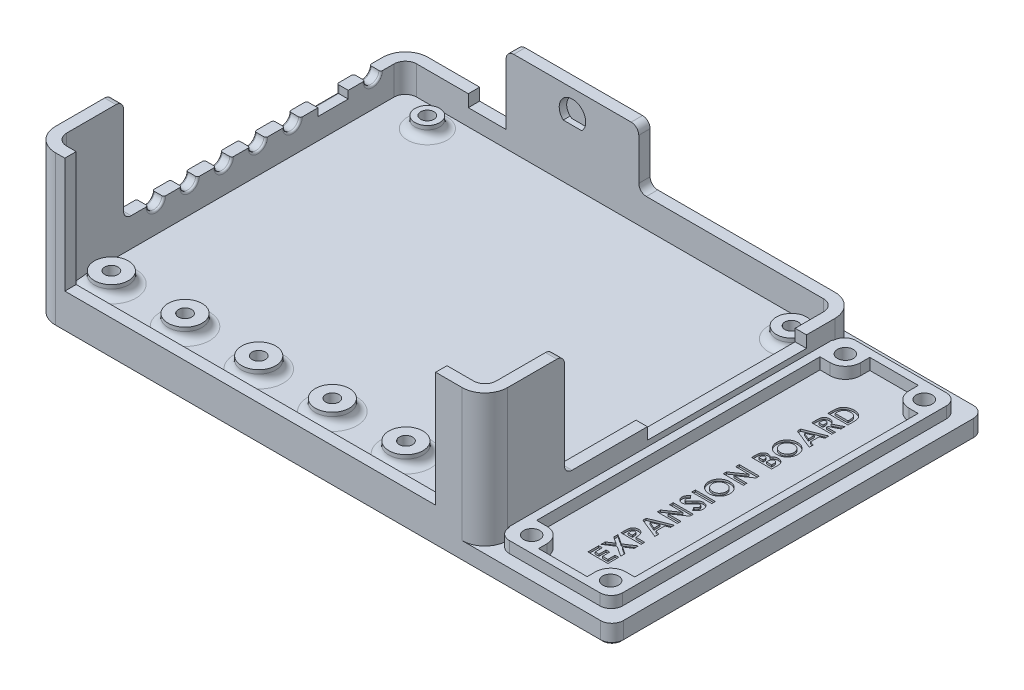
SolidWorks part; units mm, degrees
ref_plane "Front Plane" through (0, 0, 0) normal (0, 0, 1) x (1, 0, 0)
ref_plane "Top Plane" through (0, 0, 0) normal (0, 1, 0) x (1, 0, 0)
ref_plane "Right Plane" through (0, 0, 0) normal (1, 0, 0) x (0, 0, -1)
sketch "Sketch1" plane through (0, 0, 0) normal (0, 1, 0) x (1, 0, 0)
  line L1 (-53.7, 46.2) -> (53.7, 46.2)
  line L2 (-56.7, 43.2) -> (-56.7, -43.2)
  line L3 (-53.7, -46.2) -> (53.7, -46.2)
  line L4 (56.7, 43.2) -> (56.7, -43.2)
  line L5 (-56.7, 46.2) -> (56.7, -46.2) construction
  line L6 (-56.7, -46.2) -> (56.7, 46.2) construction
  arc A0 (-56.7, -43.2) -> (-53.7, -46.2) centre (-53.7, -43.2) ccw
  arc A1 (53.7, -46.2) -> (56.7, -43.2) centre (53.7, -43.2) ccw
  arc A2 (53.7, 46.2) -> (56.7, 43.2) centre (53.7, 43.2) cw
  arc A3 (-53.7, 46.2) -> (-56.7, 43.2) centre (-53.7, 43.2) ccw
  point P0 (0, 0)
  dimension "D3" = 3
  dimension "D1" = 113.4
  dimension "D2" = 92.4
extrude "Boss-Extrude1" add sketch "Sketch1" along normal blind 5
sketch "Sketch2" plane through (0, 0, 0) normal (0, -1, 0) x (1, 0, 0)
  line L12 (-56.7, 43.2) -> (-56.7, -43.2)
  line L13 (-53.7, -46.2) -> (53.7, -46.2)
  line L14 (56.7, -43.2) -> (56.7, 43.2)
  line L15 (53.7, 46.2) -> (-53.7, 46.2)
  line L16 (-56.7, 43.2) -> (-56.7, -43.2)
  line L17 (-53.7, -46.2) -> (53.7, -46.2)
  line L18 (56.7, -43.2) -> (56.7, 43.2)
  line L19 (53.7, 46.2) -> (-53.7, 46.2)
  line L24 (-59.7, 43.2) -> (-59.7, -43.2)
  line L25 (-53.7, -49.2) -> (53.7, -49.2)
  line L26 (59.7, -43.2) -> (59.7, 43.2)
  line L27 (53.7, 49.2) -> (-53.7, 49.2)
  line L28 (-59.7, 43.2) -> (-59.7, -43.2)
  line L29 (-53.7, -49.2) -> (53.7, -49.2)
  line L30 (59.7, -43.2) -> (59.7, 43.2)
  line L31 (53.7, 49.2) -> (-53.7, 49.2)
  arc A12 (-53.7, 46.2) -> (-56.7, 43.2) centre (-53.7, 43.2) ccw
  arc A13 (-56.7, -43.2) -> (-53.7, -46.2) centre (-53.7, -43.2) ccw
  arc A14 (53.7, -46.2) -> (56.7, -43.2) centre (53.7, -43.2) ccw
  arc A15 (56.7, 43.2) -> (53.7, 46.2) centre (53.7, 43.2) ccw
  arc A16 (-53.7, 46.2) -> (-56.7, 43.2) centre (-53.7, 43.2) ccw
  arc A17 (-56.7, -43.2) -> (-53.7, -46.2) centre (-53.7, -43.2) ccw
  arc A18 (53.7, -46.2) -> (56.7, -43.2) centre (53.7, -43.2) ccw
  arc A19 (56.7, 43.2) -> (53.7, 46.2) centre (53.7, 43.2) ccw
  arc A24 (-53.7, 49.2) -> (-59.7, 43.2) centre (-53.7, 43.2) ccw
  arc A25 (-59.7, -43.2) -> (-53.7, -49.2) centre (-53.7, -43.2) ccw
  arc A26 (53.7, -49.2) -> (59.7, -43.2) centre (53.7, -43.2) ccw
  arc A27 (59.7, 43.2) -> (53.7, 49.2) centre (53.7, 43.2) ccw
  arc A28 (-53.7, 49.2) -> (-59.7, 43.2) centre (-53.7, 43.2) ccw
  arc A29 (-59.7, -43.2) -> (-53.7, -49.2) centre (-53.7, -43.2) ccw
  arc A30 (53.7, -49.2) -> (59.7, -43.2) centre (53.7, -43.2) ccw
  arc A31 (59.7, 43.2) -> (53.7, 49.2) centre (53.7, 43.2) ccw
  dimension "D1" = 0
  dimension "D2" = 3
extrude "Boss-Extrude2" add sketch "Sketch2" against normal blind 40
sketch "Sketch3" plane through (0, 0, 0) normal (0, -1, 0) x (1, 0, 0)
  line L0 (53.7, 49.2) -> (-53.7, 49.2) construction
  line L1 (39.3485, 49.2) -> (94.7, 49.2)
  line L2 (39.3485, 49.2) -> (39.3485, -49.2)
  line L3 (39.3485, -49.2) -> (94.7, -49.2)
  line L4 (94.7, 49.2) -> (94.7, -49.2)
  line L5 (59.7, -43.2) -> (59.7, 43.2) construction
  line L6 (-53.7, -49.2) -> (53.7, -49.2) construction
  dimension "D1" = 35
extrude "Boss-Extrude3" add sketch "Sketch3" against normal blind 5
sketch "Sketch4" plane through (0, 40, 0) normal (0, 1, 0) x (1, 0, 0)
  line L0 (-56.7, 43.2) -> (-56.7, -43.2) construction
  line L1 (-51.2, -37.1427) -> (46.7, -37.1427)
  line L2 (-51.2, -37.1427) -> (-51.2, -59.8991)
  line L3 (-51.2, -59.8991) -> (46.7, -59.8991)
  line L4 (46.7, -37.1427) -> (46.7, -59.8991)
  line L5 (56.7, 43.2) -> (56.7, -43.2) construction
  dimension "D1" = 5.5
  dimension "D2" = 10
extrude "Cut-Extrude1" cut sketch "Sketch4" against normal offset from surface (30.4 mm away) 4.6 up to face at (0, 5, 0)
sketch "Sketch7" plane through (0, 5, 0) normal (0, 1, 0) x (1, 0, 0)
  line L0 (-51.3, -36.8) -> (45.92, -36.8) construction
  line L1 (51.042, 40.404) -> (-45.097, 40.404) construction
  line L3 (-56.7, 0) -> (56.7, 0) construction
  line L4 (-56.7, -43.2) -> (-56.7, 43.2) construction
  line L5 (56.7, -43.2) -> (56.7, 43.2) construction
  line L6 (-56.7, 43.2) -> (-56.7, -43.2) construction
  line L7 (0, 46.2) -> (0, -46.2) construction
  line L8 (-53.7, 46.2) -> (53.7, 46.2) construction
  line L9 (-53.7, -46.2) -> (53.7, -46.2) construction
  line L10 (46.7, -46.2) -> (-51.2, -46.2) construction
  circle A0 centre (-51.3, -36.8) radius 1.75
  circle A1 centre (-31.86, -36.8) radius 1.75
  circle A2 centre (-12.41, -36.8) radius 1.75
  circle A3 centre (7.03, -36.8) radius 1.75
  circle A4 centre (26.46, -36.8) radius 1.75
  circle A5 centre (45.92, -36.8) radius 1.75
  circle A6 centre (-45.097, 40.404) radius 1.75
  circle A7 centre (51.042, 40.404) radius 1.75
  circle A8 centre (-45.097, 40.404) radius 3.25
  circle A9 centre (51.042, 40.404) radius 4
  circle A10 centre (45.92, -36.8) radius 4.5
  circle A11 centre (26.46, -36.8) radius 4.5
  circle A12 centre (7.03, -36.8) radius 4.5
  circle A13 centre (-12.41, -36.8) radius 4.5
  circle A14 centre (-31.86, -36.8) radius 4.5
  circle A15 centre (-51.3, -36.8) radius 4.5
  dimension "D1" = 3.5
  dimension "D2" = 3.5
  dimension "D3" = 3.5
  dimension "D4" = 3.5
  dimension "D5" = 3.5
  dimension "D6" = 3.5
  dimension "D7" = 3.5
  dimension "D8" = 3.5
  dimension "D19" = 9
  dimension "D20" = 9
  dimension "D21" = 9
  dimension "D22" = 9
  dimension "D23" = 9
  dimension "D24" = 9
  dimension "D25" = 8
  dimension "D26" = 6.5
  dimension "D9" = 77.204
  dimension "D10" = 6.203
  dimension "D11" = 5.122
  dimension "D12" = 19.44
  dimension "D13" = 19.45
  dimension "D14" = 19.44
  dimension "D15" = 19.43
  dimension "D16" = 19.46
  dimension "D17" = 5.4
  dimension "D18" = 9.4
extrude "Boss-Extrude5" add sketch "Sketch7" along normal offset from surface (3 mm away) 1.6 up to face at (-2.25, 9.6, 47.7)
fillet "Fillet2" radius 2 8 edges at (45.92, 5, 41.3) (26.46, 5, 41.3) (7.03, 5, 41.3) (-12.41, 5, 41.3) (-31.86, 5, 41.3) (-51.3, 5, 41.3) (51.042, 5, -36.404) (-45.097, 5, -37.154)
sketch "Sketch11" plane through (-59.7, 0, 0) normal (-1, 0, 0) x (0, 0, 1)
  line L0 (-37.613, 12.6) -> (19.667, 12.6) construction
  line L1 (43.2, 0) -> (-43.2, 0) construction
  line L3 (-37.613, 12.6) -> (-43.2, 12.6) construction
  line L4 (-43.2, 40) -> (-43.2, 0) construction
  circle A0 centre (19.667, 12.6) radius 2.1
  circle A1 centre (10.777, 12.6) radius 2.1
  circle A2 centre (1.757, 12.6) radius 2.1
  circle A3 centre (-7.26, 12.6) radius 2.1
  circle A4 centre (-16.404, 12.6) radius 2.1
  circle A5 centre (-37.613, 12.6) radius 2.1
  dimension "D7" = 4.2
  dimension "D8" = 4.2
  dimension "D9" = 4.2
  dimension "D10" = 4.2
  dimension "D11" = 4.2
  dimension "D12" = 4.2
  dimension "D1" = 12.6
  dimension "D2" = 21.209
  dimension "D3" = 9.144
  dimension "D4" = 9.017
  dimension "D5" = 9.02
  dimension "D6" = 8.89
  dimension "D13" = 5.587
extrude "Cut-Extrude4" cut sketch "Sketch11" against normal blind 9.6
sketch "Sketch12" plane through (-59.7, 0, 0) normal (-1, 0, 0) x (0, 0, 1)
  line L0 (43.2, 40) -> (-43.2, 40) construction
  line L1 (28.2, 40) -> (-56.9577, 40)
  line L2 (28.2, 40) -> (28.2, 12.6)
  line L3 (28.2, 12.6) -> (-56.9577, 12.6)
  line L4 (-56.9577, 40) -> (-56.9577, 12.6)
  line L5 (43.2, 0) -> (-43.2, 0) construction
  dimension "D1" = 21
  dimension "D2" = 12.6
extrude "Cut-Extrude5" cut sketch "Sketch12" against normal through all
sketch "Sketch13" plane through (0, 12.6, 0) normal (0, 1, 0) x (1, 0, 0)
  line L0 (-45.097, 40.404) -> (-35.077, 40.404) construction
  line L2 (-40.077, 53.0138) -> (-30.077, 53.0138)
  line L3 (-40.077, 53.0138) -> (-40.077, 27.7942)
  line L4 (-40.077, 27.7942) -> (-30.077, 27.7942)
  line L5 (-30.077, 53.0138) -> (-30.077, 27.7942)
  line L6 (-40.077, 53.0138) -> (-30.077, 27.7942) construction
  line L7 (-40.077, 27.7942) -> (-30.077, 53.0138) construction
  dimension "D1" = 10.02
  dimension "D2" = 10
extrude "Cut-Extrude6" cut sketch "Sketch13" against normal offset from surface (3.2 mm away) 1.4 up to face at (-45.097, 8, -38.654)
sketch "Sketch14" plane through (0, 12.6, 0) normal (0, 1, 0) x (1, 0, 0)
  line L0 (51.042, 40.404) -> (51.042, 35.704) construction
  line L1 (45.5852, 35.704) -> (71.3808, 35.704)
  line L2 (45.5852, 35.704) -> (45.5852, -6.296)
  line L3 (45.5852, -6.296) -> (71.3808, -6.296)
  line L4 (71.3808, 35.704) -> (71.3808, -6.296)
  dimension "D1" = 42
  dimension "D2" = 4.7
extrude "Cut-Extrude7" cut sketch "Sketch14" against normal offset from surface (3.1 mm away) 1.5 up to face at (51.042, 8, -38.654)
sketch "Sketch15" plane through (0, 12.6, 0) normal (0, 1, 0) x (1, 0, 0)
  line L0 (53.7, 46.2) -> (-30.077, 46.2) construction
  line L1 (-30.077, 49.2) -> (4.923, 49.2)
  line L2 (-30.077, 49.2) -> (-30.077, 46.2)
  line L3 (-30.077, 46.2) -> (4.923, 46.2)
  line L4 (4.923, 49.2) -> (4.923, 46.2)
  dimension "D1" = 35
extrude "Boss-Extrude6" add sketch "Sketch15" along normal blind 15
fillet "Fillet3" radius 2 7 edges at (-58.2, 40, 28.2) (58.2, 40, 28.2) (58.2, 12.6, 28.2) (4.923, 12.6, -47.7) (4.923, 27.6, -47.7) (-30.077, 27.6, -47.7) (-58.2, 12.6, 28.2)
sketch "Sketch16" plane through (0, 0, -49.2) normal (0, 0, -1) x (-1, 0, 0)
  line L0 (10.1275, 19.1) -> (15.0265, 19.1)
  line L2 (-46.7, 9.6) -> (51.2, 9.6) construction
  line L3 (30.077, 25.6) -> (30.077, 9.4) construction
  arc A0 (15.0265, 19.1) -> (10.1275, 19.1) centre (12.577, 21.6) ccw
  dimension "D1" = 7
  dimension "D2" = 2.5
  dimension "D3" = 12
  dimension "D4" = 17.5
extrude "Cut-Extrude8" cut sketch "Sketch16" against normal up to surface (3 mm away) up to face at (-3.1349, 14.0416, -46.2)
sketch "Sketch17" plane through (0, 0, -49.2) normal (0, 0, -1) x (-1, 0, 0)
  circle A0 centre (12.577, 21.6) radius 3.0287
extrude "Boss-Extrude7" add sketch "Sketch17" against normal blind 1.5
sketch "Sketch18" plane through (0, 8, 0) normal (0, 1, 0) x (1, 0, 0)
  circle A0 centre (-51.3, -36.8) radius 1.75
  circle A1 centre (-31.86, -36.8) radius 1.75
  circle A2 centre (-12.41, -36.8) radius 1.75
  circle A3 centre (7.03, -36.8) radius 1.75
  circle A4 centre (26.46, -36.8) radius 1.75
  circle A5 centre (45.92, -36.8) radius 1.75
  circle A6 centre (51.042, 40.404) radius 1.75
  circle A7 centre (-45.097, 40.404) radius 1.75
extrude "Cut-Extrude9" cut sketch "Sketch18" against normal through all
sketch "Sketch19" plane through (0, 0, 0) normal (0, -1, 0) x (1, 0, 0)
  circle A0 centre (-51.3, 36.8) radius 2.9
  circle A1 centre (-31.86, 36.8) radius 2.9
  circle A2 centre (-12.41, 36.8) radius 2.9
  circle A3 centre (7.03, 36.8) radius 2.9
  circle A4 centre (26.46, 36.8) radius 2.9
  circle A5 centre (45.92, 36.8) radius 2.9
  circle A6 centre (51.042, -40.404) radius 2.9
  circle A7 centre (-45.097, -40.404) radius 2.9
  dimension "D1" = 5.8
  dimension "D2" = 5.8
  dimension "D3" = 5.8
  dimension "D4" = 5.8
  dimension "D5" = 5.8
  dimension "D6" = 5.8
  dimension "D7" = 5.8
  dimension "D8" = 5.8
extrude "Cut-Extrude10" cut sketch "Sketch19" against normal offset from surface (3.5 mm away) 1.5 up to face at (45.92, 5, 43.3)
sketch "Sketch20" plane through (0, 5, 0) normal (0, 1, 0) x (1, 0, 0)
  line L0 (64.6, 41.068) -> (64.6, -41.736) construction
  line L1 (64.6, -41.736) -> (85.428, -41.736) construction
  line L2 (85.428, -41.736) -> (85.428, 41.068) construction
  line L3 (85.428, 41.068) -> (64.6, 41.068) construction
  line L4 (59.7, -43.2) -> (59.7, 43.2) construction
  line L5 (62.9, 45.513) -> (86.8, 45.513)
  line L6 (59.9, 42.513) -> (59.9, -42.937)
  line L7 (62.9, -45.937) -> (86.8, -45.937)
  line L8 (89.8, 42.513) -> (89.8, -42.937)
  line L9 (51.042, 40.404) -> (51.042, 34.21) construction
  line L10 (51.042, 34.21) -> (76.3886, 34.21) construction
  line L11 (76.3886, 34.21) -> (76.3886, 41.068) construction
  line L12 (61.9, 37.068) -> (61.9, -37.736)
  line L13 (68.6, -43.937) -> (81.428, -43.937)
  line L14 (87.8, 37.068) -> (87.8, -37.736)
  line L16 (64.6, 37.068) -> (61.9, 37.068)
  line L17 (68.6, 41.068) -> (68.6, 43.513)
  line L18 (81.428, 41.068) -> (81.428, 43.513)
  line L19 (85.428, 37.068) -> (87.8, 37.068)
  line L20 (64.6, -37.736) -> (61.9, -37.736)
  line L21 (68.6, -41.736) -> (68.6, -43.937)
  line L22 (81.428, -41.736) -> (81.428, -43.937)
  line L23 (85.428, -37.736) -> (87.8, -37.736)
  line L24 (62.9, -43.937) -> (86.8, -43.937) construction
  line L25 (61.9, 42.513) -> (61.9, -42.937) construction
  line L26 (87.8, 42.513) -> (87.8, -42.937) construction
  line L27 (62.9, 43.513) -> (86.8, 43.513) construction
  line L28 (68.6, 43.513) -> (81.428, 43.513)
  circle A0 centre (64.6, 41.068) radius 2.1
  circle A1 centre (85.428, 41.068) radius 2.1
  circle A2 centre (85.428, -41.736) radius 2.1
  circle A3 centre (64.6, -41.736) radius 2.1
  arc A4 (59.9, -42.937) -> (62.9, -45.937) centre (62.9, -42.937) ccw
  arc A5 (86.8, -45.937) -> (89.8, -42.937) centre (86.8, -42.937) ccw
  arc A6 (86.8, 45.513) -> (89.8, 42.513) centre (86.8, 42.513) cw
  arc A7 (62.9, 45.513) -> (59.9, 42.513) centre (62.9, 42.513) ccw
  arc A12 (64.6, 37.068) -> (68.6, 41.068) centre (64.6, 41.068) ccw
  arc A13 (81.428, 41.068) -> (85.428, 37.068) centre (85.428, 41.068) ccw
  arc A14 (68.6, -41.736) -> (64.6, -37.736) centre (64.6, -41.736) ccw
  arc A15 (85.428, -37.736) -> (81.428, -41.736) centre (85.428, -41.736) ccw
  arc A16 (61.9, -42.937) -> (62.9, -43.937) centre (62.9, -42.937) ccw construction
  arc A17 (86.8, -43.937) -> (87.8, -42.937) centre (86.8, -42.937) ccw construction
  arc A18 (86.8, 43.513) -> (87.8, 42.513) centre (86.8, 42.513) cw construction
  arc A19 (62.9, 43.513) -> (61.9, 42.513) centre (62.9, 42.513) ccw construction
  point P23 (89.8, -45.937)
  point P26 (89.8, 45.513)
  point P29 (59.9, 45.513)
  dimension "D10" = 3
  dimension "D12" = 8
  dimension "D13" = 8
  dimension "D14" = 8
  dimension "D15" = 8
  dimension "D16" = 4.2
  dimension "D17" = 4.2
  dimension "D18" = 4.2
  dimension "D19" = 4.2
  dimension "D1" = 82.804
  dimension "D2" = 20.828
  dimension "D3" = 4.445
  dimension "D4" = 4.7
  dimension "D5" = 29.9
  dimension "D6" = 0.2
  dimension "D7" = 6.194
  dimension "D8" = 6.858
  dimension "D9" = 91.45
  dimension "D11" = 2
extrude "Boss-Extrude8" add sketch "Sketch20" along normal up to surface (3 mm away) up to face at (45.92, 8, 38.55)
sketch "Sketch21" plane through (0, 5, 0) normal (0, 1, 0) x (1, 0, 0)
  line L0 (78.1776, -35.8007) -> (78.1776, 35.1839) construction
  text T0 "<b>EXPANSION BOARD</b>" font "Century Gothic" height in points 20
extrude "Cut-Extrude11" cut sketch "Sketch21" against normal blind 0.5
sketch "Sketch22" plane through (0, 5, 0) normal (0, 1, 0) x (1, 0, 0)
  line L0 (89.8, -42.937) -> (89.8, 42.513) construction
  line L1 (93.25, 52.1113) -> (108.1813, 52.1113)
  line L2 (93.25, 52.1113) -> (93.25, -51.7076)
  line L3 (93.25, -51.7076) -> (108.1813, -51.7076)
  line L4 (108.1813, 52.1113) -> (108.1813, -51.7076)
  dimension "D1" = 3.45
extrude "Cut-Extrude12" cut sketch "Sketch22" against normal through all
fillet "Fillet4" radius 3 2 edges at (93.25, 2.5, 49.2) (93.25, 2.5, -49.2)
chamfer "Chamfer1" distance 0.6 angle 45 16 edges at (92.3713, 0, -48.3213) (18.275, 0, -49.2) (-57.9426, 0, -47.4426) (-59.7, 0, 0) (-57.9426, 0, 47.4426) (18.275, 0, 49.2) (92.3713, 0, 48.3213) (93.25, 0, 0) (-31.86, 0, 33.9) (-12.41, 0, 33.9) (7.03, 0, 33.9) (26.46, 0, 33.9) (45.92, 0, 33.9) (51.042, 0, -43.304) (-45.097, 0, -43.304) (-51.3, 0, 33.9)
sketch "Sketch23" plane through (0, 5, 0) normal (0, 1, 0) x (1, 0, 0)
  circle A0 centre (64.6, 41.068) radius 2.1
  circle A1 centre (85.428, 41.068) radius 2.1
  circle A2 centre (64.6, -41.736) radius 2.1
  circle A3 centre (85.428, -41.736) radius 2.1
extrude "Cut-Extrude13" cut sketch "Sketch23" against normal offset from surface (3 mm away) 2 up to face at (17.3697, 0, 0)
sketch "Sketch26" plane through (0, 8, 0) normal (0, 1, 0) x (1, 0, 0)
  line L1 (59.9, 42.513) -> (58.6453, 42.513)
  line L2 (59.9, 42.513) -> (59.9, -42.937)
  line L3 (59.9, -42.937) -> (58.6453, -42.937)
  line L4 (58.6453, 42.513) -> (58.6453, -42.937)
extrude "Boss-Extrude10" add sketch "Sketch26" against normal up to surface (8 mm away) up to face at (17.3697, 0, 0)
fillet "Fillet5" radius 0.5 12 edges at (-59.7, 10.5, -37.613) (-59.7, 10.5, -16.404) (-59.7, 10.5, -7.26) (-59.7, 10.5, 1.757) (-59.7, 10.5, 10.777) (-59.7, 10.5, 19.667) (-56.7, 10.5, 19.667) (-56.7, 10.5, 10.777) (-56.7, 10.5, 1.757) (-56.7, 10.5, -7.26) (-56.7, 10.5, -16.404) (-56.7, 10.5, -37.613)
sketch "Sketch29" plane through (0, 12.6, 0) normal (0, 1, 0) x (1, 0, 0)
  line L0 (-56.7, 31.1209) -> (-59.7, 31.1209)
  line L1 (-56.7, 35.013) -> (-56.7, 19.004) construction
  line L2 (-59.7, 35.013) -> (-59.7, 19.004) construction
  line L3 (-59.7, 31.1209) -> (-59.7, 23.1157)
  line L4 (-59.7, 23.1157) -> (-56.7, 23.1157)
  line L5 (-56.7, 23.1157) -> (-56.7, 31.1209)
extrude "Cut-Extrude14" cut sketch "Sketch29" against normal blind 2
fillet "Fillet6" radius 0.5 3 edges at (-59.7, 10.6, -27.1183) (-59.7, 11.6, -23.1157) (-59.7, 11.6, -31.1209)
